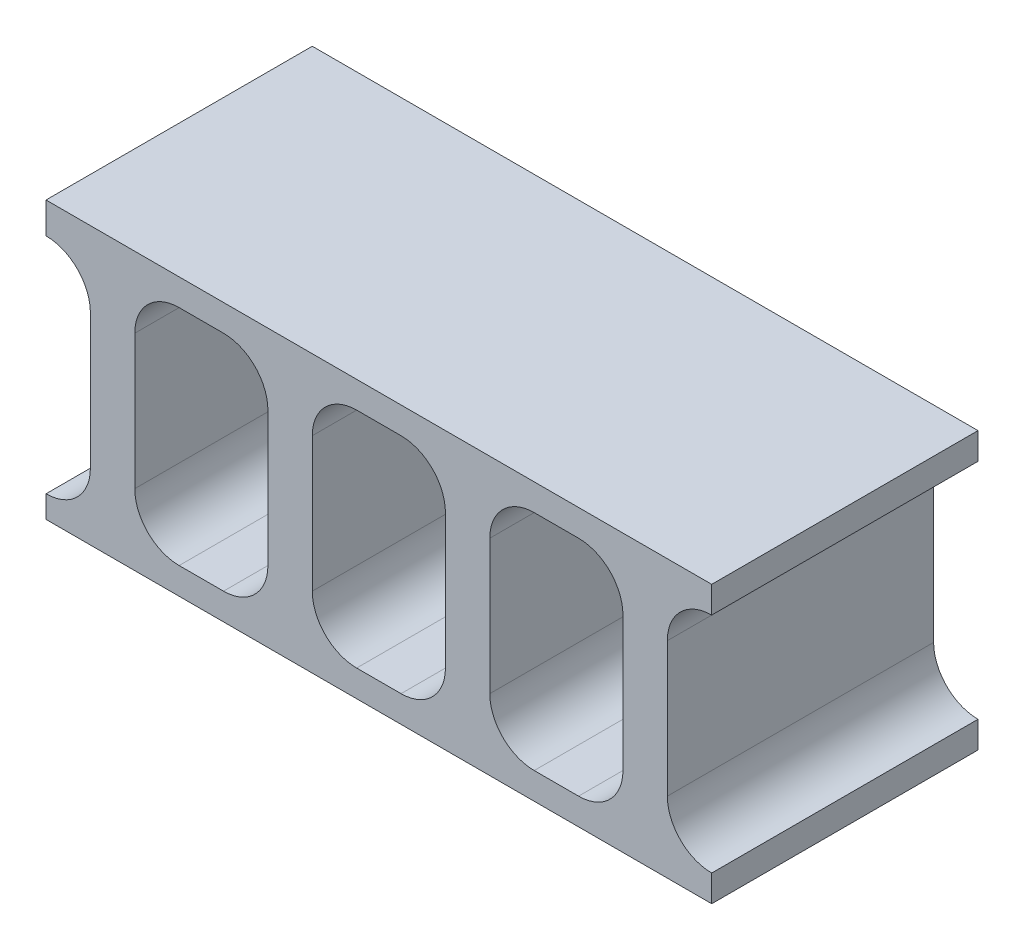
SolidWorks part; units mm, degrees
ref_plane "前基準面" through (0, 0, 0) normal (0, 0, 1) x (1, 0, 0)
ref_plane "上基準面" through (0, 0, 0) normal (0, 1, 0) x (1, 0, 0)
ref_plane "右基準面" through (0, 0, 0) normal (1, 0, 0) x (0, 0, -1)
sketch "草圖1" plane through (0, 0, 0) normal (0, 0, 1) x (1, 0, 0)
  line L0 (-23.5, 11.4167) -> (51.5, 11.4167)
  line L1 (51.5, 11.4167) -> (51.5, 8.4167)
  line L2 (51.5, 8.4167) -> (46.5, 8.4167)
  line L3 (46.5, 8.4167) -> (46.5, -16.75)
  line L4 (46.5, -16.75) -> (51.5, -16.75)
  line L5 (51.5, -16.75) -> (51.5, -19.75)
  line L6 (51.5, -19.75) -> (-23.5, -19.75)
  line L7 (-23.5, -19.75) -> (-23.5, -17.25)
  line L8 (-23.5, -17.25) -> (-18.5, -17.25)
  line L9 (-18.5, -17.25) -> (-18.5, 7.9167)
  line L10 (-18.5, 7.9167) -> (-23.5, 7.9167)
  line L11 (-23.5, 7.9167) -> (-23.5, 11.4167)
  line L13 (-13.5, 8.4167) -> (1.5, 8.4167)
  line L14 (-13.5, 8.4167) -> (-13.5, -16.75)
  line L15 (-13.5, -16.75) -> (1.5, -16.75)
  line L16 (1.5, 8.4167) -> (1.5, -16.75)
  line L17 (6.5, 8.4167) -> (21.5, 8.4167)
  line L18 (6.5, 8.4167) -> (6.5, -16.75)
  line L19 (6.5, -16.75) -> (21.5, -16.75)
  line L20 (21.5, 8.4167) -> (21.5, -16.75)
  line L21 (26.5, 8.4167) -> (41.5, 8.4167)
  line L22 (26.5, 8.4167) -> (26.5, -16.75)
  line L23 (26.5, -16.75) -> (41.5, -16.75)
  line L24 (41.5, 8.4167) -> (41.5, -16.75)
  dimension "D1" = 75
  dimension "D2" = 5
  dimension "D3" = 5
  dimension "D4" = 5
  dimension "D5" = 5
  dimension "D6" = 3
  dimension "D7" = 3
  dimension "D8" = 3
  dimension "D9" = 3
  dimension "D10" = 3
  dimension "D11" = 3
  dimension "D12" = 5
  dimension "D13" = 5
  dimension "D14" = 5
  dimension "D15" = 5
  dimension "D16" = 15
  dimension "D17" = 15
  dimension "D18" = 15
extrude "填料-伸長1" add sketch "草圖1" along normal blind 30
fillet "圓角1" radius 5 1 edges at (-18.5, 7.9167, 15)
fillet "圓角2" radius 5 1 edges at (-18.5, -17.25, 15)
fillet "圓角3" radius 5 14 edges at (46.5, 8.4167, 15) (46.5, -16.75, 15) (41.5, -16.75, 15) (21.5, -16.75, 15) (26.5, -16.75, 15) (6.5, -16.75, 15) (41.5, 8.4167, 15) (21.5, 8.4167, 15) (26.5, 8.4167, 15) (6.5, 8.4167, 15) (-13.5, 8.4167, 15) (-13.5, -16.75, 15) (1.5, 8.4167, 15) (1.5, -16.75, 15)
